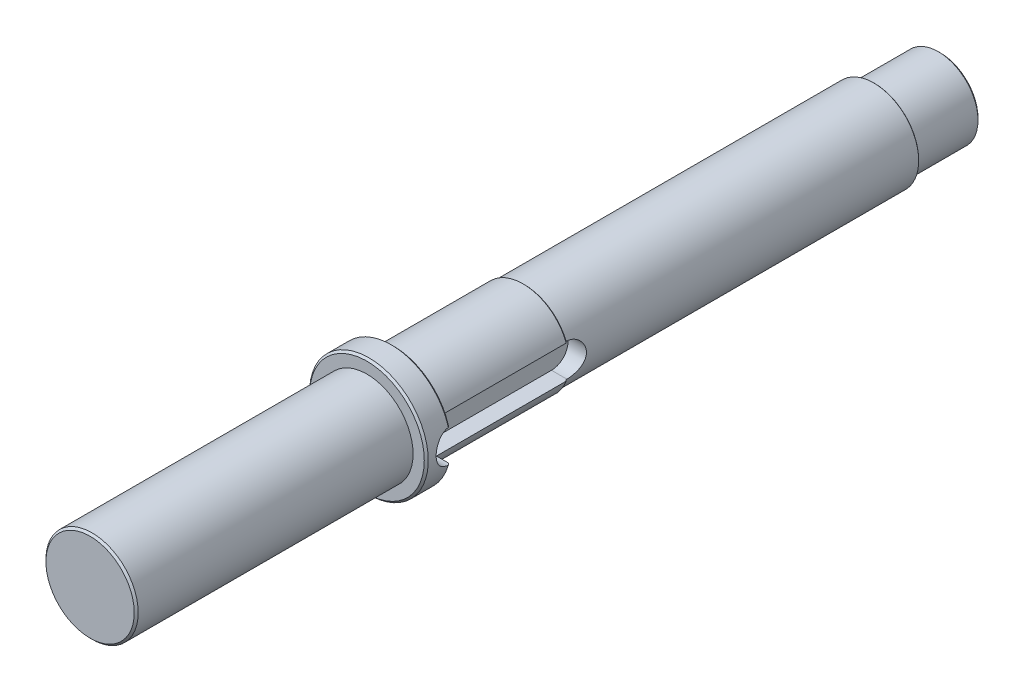
SolidWorks part; units mm, degrees
material "镀铬不锈钢"
ref_plane "前视基准面" through (0, 0, 0) normal (0, 0, 1) x (1, 0, 0)
ref_plane "上视基准面" through (0, 0, 0) normal (0, 1, 0) x (1, 0, 0)
ref_plane "右视基准面" through (0, 0, 0) normal (1, 0, 0) x (0, 0, -1)
sketch "Sketch1" plane through (0, 0, 0) normal (0, 0, 1) x (1, 0, 0)
  circle A0 centre (0, 0) radius 7
  dimension "D1" = 14
extrude "Extrude1" add sketch "Sketch1" along normal blind 129
sketch "Sketch2" plane through (0, 0, 129) normal (0, 0, 1) x (1, 0, 0)
  circle A2 centre (0, 0) radius 9
  circle A3 centre (0, 0) radius 9
  dimension "D1" = 2
extrude "Extrude2" add sketch "Sketch2" along normal blind 4 from offset 46 offset against normal yes
sketch "Sketch3" plane through (0, 0, 0) normal (1, 0, 0) x (0, 0, -1)
  line L0 (-83, 0) -> (-63, 0) construction
  line L1 (-83, -7) -> (-83, 7) construction
  line L2 (-83, 2.5) -> (-63, 2.5)
  line L3 (-83, -2.5) -> (-63, -2.5)
  arc A0 (-83, 2.5) -> (-83, -2.5) centre (-83, 0) ccw
  arc A1 (-63, -2.5) -> (-63, 2.5) centre (-63, 0) ccw
  point P5 (-73, 0)
  dimension "D1" = 5
  dimension "D2" = 20
extrude "Extrude3" cut sketch "Sketch3" along normal through all from offset 4
sketch "Sketch4" plane through (0, 0, 0) normal (0, 0, -1) x (-1, 0, 0)
  circle A0 centre (0, 0) radius 6
  dimension "D1" = 12
extrude "Extrude4" cut sketch "Sketch4" against normal blind 10 flip side to cut
chamfer "Chamfer1" distance 0.3 angle 45 5 edges at (-6, 0, 0) (7, 0, 129) (9, 0, 87) (-9, 0, 83) (-7, 0, 10)
sketch "Sketch5" plane through (0, 0, 0) normal (0, 0, -1) x (-1, 0, 0)
  circle A0 centre (0, 0) radius 6.8
  dimension "D1" = 13.6
extrude "Extrude5" cut sketch "Sketch5" against normal offset from surface (63 mm away) 20 flip side to cut up to face at (-0.2071, 0, 83)
chamfer "Chamfer2" distance 0.3 angle 45 1 edges at (-7, 0, 63)
